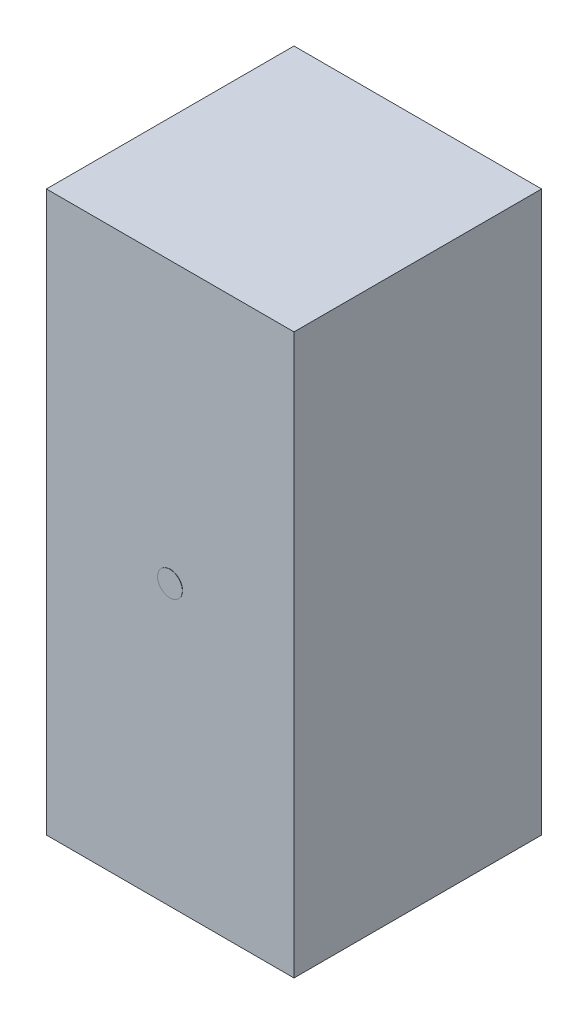
SolidWorks part; units mm, degrees
ref_plane "Alzado" through (0, 0, 0) normal (0, 0, 1) x (1, 0, 0)
ref_plane "Planta" through (0, 0, 0) normal (0, 1, 0) x (1, 0, 0)
ref_plane "Vista lateral" through (0, 0, 0) normal (1, 0, 0) x (0, 0, -1)
sketch "Sketch1" plane through (0, 0, 0) normal (0, 1, 0) x (1, 0, 0)
  line L1 (-50, 50) -> (50, 50)
  line L2 (-50, 50) -> (-50, -50)
  line L3 (-50, -50) -> (50, -50)
  line L4 (50, 50) -> (50, -50)
  line L5 (-50, 50) -> (50, -50) construction
  line L6 (-50, -50) -> (50, 50) construction
  point P0 (0, 0)
  dimension "D1" = 100
  dimension "D2" = 100
extrude "Boss-Extrude1" add sketch "Sketch1" along normal blind 226
sketch "Sketch2" plane through (0, 0, 50) normal (0, 0, 1) x (1, 0, 0)
  line L0 (-50, 226) -> (-50, 0) construction
  circle A0 centre (0, 113) radius 5
  point P4 (-50, 113)
  point P5 (0, 0)
  dimension "D1" = 10
extrude "Boss-Extrude2" add sketch "Sketch2" along normal blind 0.1
